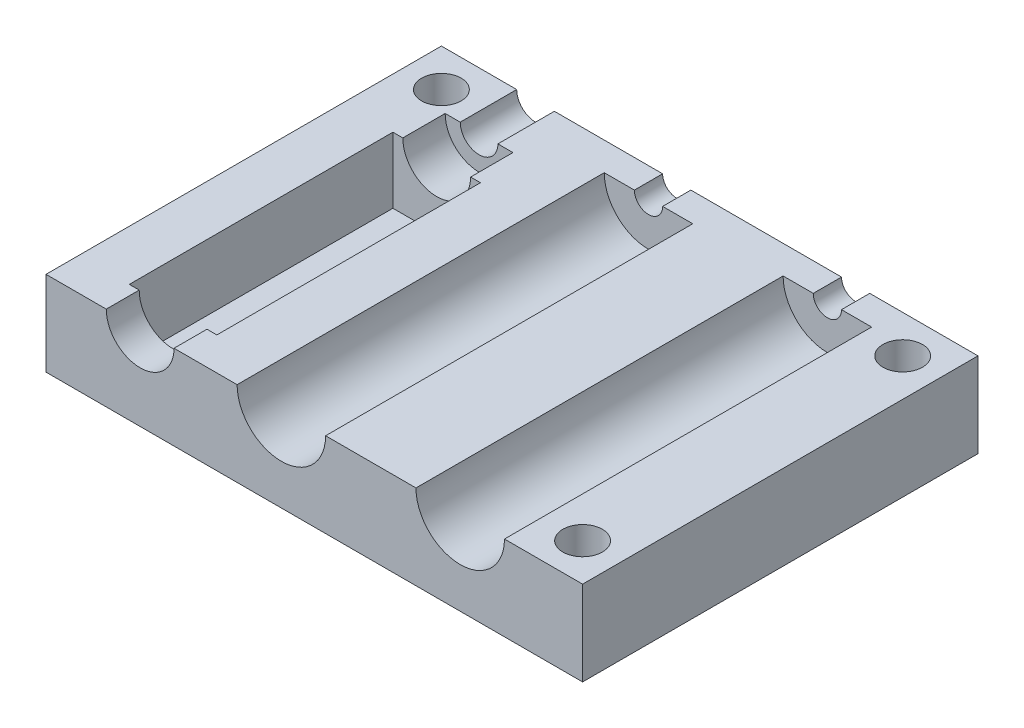
SolidWorks part; units mm, degrees
ref_plane "Alzado" through (0, 0, 0) normal (0, 0, 1) x (1, 0, 0)
ref_plane "Planta" through (0, 0, 0) normal (0, 1, 0) x (1, 0, 0)
ref_plane "Vista lateral" through (0, 0, 0) normal (1, 0, 0) x (0, 0, -1)
sketch "Croquis1" plane through (0, 0, 0) normal (0, 0, 1) x (1, 0, 0)
  line L0 (-28.5, 1) -> (-22.1, 1)
  line L1 (-28.5, 8) -> (28.5, 8)
  line L2 (-28.5, 8) -> (-28.5, -8)
  line L3 (-28.5, -8) -> (28.5, -8)
  line L4 (28.5, 8) -> (28.5, -8)
  line L5 (-28.5, 8) -> (28.5, -8) construction
  line L6 (-28.5, -8) -> (28.5, 8) construction
  line L7 (-14.9, 1) -> (-8.2, 1)
  line L8 (1.2, 1) -> (10.8, 1)
  line L9 (20.2, 1) -> (28.5, 1)
  circle A0 centre (-18.5, 1) radius 3.6
  circle A1 centre (-3.5, 1) radius 4.7
  circle A2 centre (15.5, 1) radius 4.7
  circle A3 centre (-3.5, 1) radius 8.5 construction
  circle A4 centre (15.5, 1) radius 8.5 construction
  point P0 (0, 0)
  dimension "D3" = 7.2
  dimension "D6" = 9.4
  dimension "D8" = 9.4
  dimension "D10" = 17
  dimension "D11" = 17
  dimension "D1" = 57
  dimension "D2" = 16
  dimension "D4" = 9
  dimension "D5" = 10
  dimension "D7" = 15
  dimension "D9" = 19
extrude "Saliente-Extruir1" add sketch "Croquis1" against normal blind 39 contours A2 L8 A1 L7 A0 L0 L2 L3 L4 L9 region at (-0.094, -4.0537, 0)
sketch "Croquis2" plane through (0, 1, 0) normal (0, 1, 0) x (1, 0, 0)
  line L0 (-18.5, 0) -> (-18.5, 39) construction
  line L1 (-22.1, 0) -> (-14.9, 0) construction
  line L2 (-14.9, 39) -> (-22.1, 39) construction
  line L3 (-14.9, 0) -> (-8.2, 0) construction
  line L4 (-23.15, 35.5) -> (-13.85, 35.5)
  line L5 (-23.15, 35.5) -> (-23.15, 3.5)
  line L6 (-23.15, 3.5) -> (-13.85, 3.5)
  line L7 (-13.85, 35.5) -> (-13.85, 3.5)
  line L8 (-23.15, 35.5) -> (-13.85, 3.5) construction
  line L9 (-23.15, 3.5) -> (-13.85, 35.5) construction
  line L10 (-23.15, 31.5) -> (-13.85, 31.5)
  point P6 (-18.5, 19.5)
  line M9 (-14.9, 39) -> (-14.9, 0)
  dimension "D1" = 9.3
  dimension "D2" = 3.5
  dimension "D3" = 28
extrude "Cortar-Extruir1" cut sketch "Croquis2" against normal blind 7 contours L10 L5 L6 M9 | L10 L6 L7 M9 region at (-19.025, 1, -17.5) region at (-14.375, 1, -17.5)
sketch "Croquis3" plane through (0, 0, -39) normal (0, 0, -1) x (-1, 0, 0)
  line L0 (28.5, 1) -> (22.1, 1) construction
  line L1 (-28.5, -8) -> (28.5, -8)
  line L2 (-28.5, -8) -> (-28.5, 1)
  line L3 (-28.5, 1) -> (28.5, 1)
  line L4 (28.5, -8) -> (28.5, 1)
  line L5 (28.5, 1) -> (28.5, -8) construction
  line L7 (28.5, -8) -> (13.5, -8)
  line L8 (28.5, -8) -> (28.5, 1)
  line L9 (28.5, 1) -> (13.5, 1)
  line L10 (13.5, -8) -> (13.5, 1)
  circle A0 centre (-15.5, 1) radius 1.5
  circle A1 centre (3.5, 1) radius 1.5
  circle A2 centre (18.5, 1) radius 2
  arc M5 (-10.8, 1) -> (-20.2, 1) centre (-15.5, 1) cw
  line M6 (-20.2, 1) -> (-28.5, 1)
  line M7 (-28.5, 1) -> (-28.5, -8)
  line M8 (-28.5, -8) -> (28.5, -8)
  line M9 (28.5, -8) -> (28.5, 1)
  line M10 (28.5, 1) -> (22.1, 1)
  arc M11 (22.1, 1) -> (14.9, 1) centre (18.5, 1) cw
  line M12 (14.9, 1) -> (8.2, 1)
  arc M13 (8.2, 1) -> (-1.2, 1) centre (3.5, 1) cw
  line M14 (-1.2, 1) -> (-10.8, 1)
  dimension "D2" = 3
  dimension "D3" = 3
  dimension "D4" = 4
  dimension "D1" = 15
extrude "Saliente-Extruir4" add sketch "Croquis3" along normal blind 3 contours L3 M5 | L10 L3 M8 M13 M14 M5 M6 M7 | L3 M13 region at (7.8373, -4.0634, -39) region at (15.5, -1.1488, -39) region at (-3.5, -1.1488, -39)
extrude "Saliente-Extruir5" add sketch "Croquis3<4>" along normal mid plane 6 contours L10 L1 M9 M10 M11 M12 | L3 M11 region at (-21.4439, -4.0278, -39) region at (-15.7, 0.9195, -39)
sketch "Croquis3<4>" plane through (0, 0, -39) normal (0, 0, -1) x (-1, 0, 0) same geometry as "Croquis3"
sketch "Croquis4" plane through (0, 1, 0) normal (0, 1, 0) x (1, 0, 0)
  line L0 (-5, 42) -> (-16.5, 42) construction
  line L1 (28.5, 42) -> (28.5, 0) construction
  line L2 (20.2, 0) -> (28.5, 0) construction
  line L3 (-28.5, 42) -> (-28.5, 0) construction
  circle A0 centre (-24.5, 38) radius 2.1
  circle A1 centre (24.5, 38) radius 2.1
  circle A2 centre (24.5, 4) radius 2.1
  dimension "D1" = 4.2
  dimension "D2" = 4.2
  dimension "D5" = 4.2
  dimension "D3" = 4
  dimension "D4" = 4
  dimension "D6" = 4
  dimension "D7" = 4
  dimension "D8" = 4
extrude "Cortar-Extruir2" cut sketch "Croquis4" against normal through all
